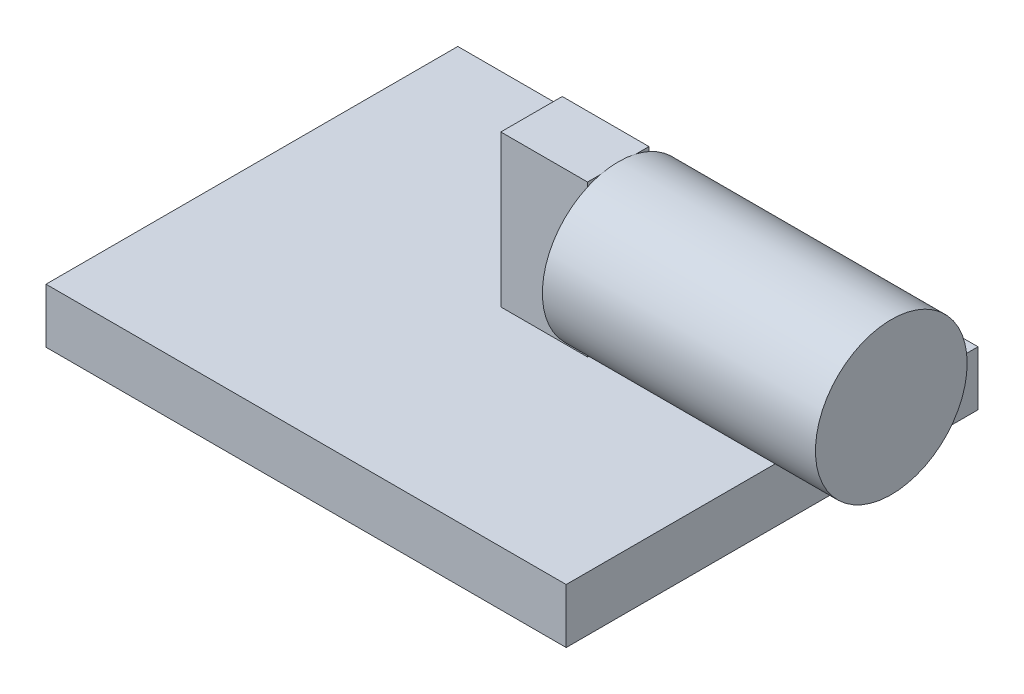
SolidWorks part; units mm, degrees
ref_plane "Front Plane" through (0, 0, 0) normal (0, 0, 1) x (1, 0, 0)
ref_plane "Top Plane" through (0, 0, 0) normal (0, 1, 0) x (1, 0, 0)
ref_plane "Right Plane" through (0, 0, 0) normal (1, 0, 0) x (0, 0, -1)
sketch "Sketch1" plane through (0, 0, 0) normal (0, 1, 0) x (1, 0, 0)
  line L1 (-9.525, -7.5406) -> (9.525, -7.5406)
  line L2 (-9.525, -7.5406) -> (-9.525, 7.5406)
  line L3 (-9.525, 7.5406) -> (9.525, 7.5406)
  line L4 (9.525, -7.5406) -> (9.525, 7.5406)
  line L5 (-9.525, -7.5406) -> (9.525, 7.5406) construction
  line L6 (-9.525, 7.5406) -> (9.525, -7.5406) construction
  point P0 (0, 0)
  dimension "D1" = 15.0813
  dimension "D2" = 19.05
extrude "Board" add sketch "Sketch1" along normal blind 2
ref_plane "Front of Barrel" through (12.7, 0, 0) normal (1, 0, 0) x (0, 0, -1)
sketch "Sketch2" plane through (12.7, 0, 0) normal (1, 0, 0) x (0, 0, -1)
  line L0 (-7.5406, 2) -> (7.5406, 2) construction
  line L1 (7.5406, 2) -> (7.5406, 0) construction
  circle A0 centre (1.1906, 4.85) radius 2.7781
  dimension "D1" = 5.5562
  dimension "D2" = 2.85
  dimension "D3" = 6.35
extrude "LaserBarrel" add sketch "Sketch2" against normal blind 10 separate body
sketch "Sketch4" plane through (2.7, 0, 0) normal (-1, 0, 0) x (0, 0, 1)
  line L0 (-7.5406, 2) -> (7.5406, 2) construction
  line L1 (-2.3156, 7.55) -> (-0.0656, 7.55)
  line L2 (-2.3156, 7.55) -> (-2.3156, 2)
  line L3 (-2.3156, 2) -> (-0.0656, 2)
  line L4 (-0.0656, 7.55) -> (-0.0656, 2)
  line L5 (-1.1906, 7.6281) -> (-1.1906, 2.0719) construction
  circle A0 centre (-1.1906, 4.85) radius 2.7781 construction
  point P11 (-1.1906, 7.55)
  dimension "D1" = 5.55
  dimension "D2" = 2.25
extrude "Barrel Butt Mount" add sketch "Sketch4" along normal blind 3.175
ref_axis "Axis1" through (2.7, 4.85, -1.1906) along (1, 0, 0)
ref_plane "Centerline of Barrel" through (0, 0, -1.1906) normal (0, 0, 1) x (1, 0, 0)
sketch "Centerline of Board" plane through (0, 2, 0) normal (0, 1, 0) x (1, 0, 0)
  line L0 (-9.525, 7.5406) -> (-9.525, -7.5406) construction
  point P0 (-9.525, 0)
